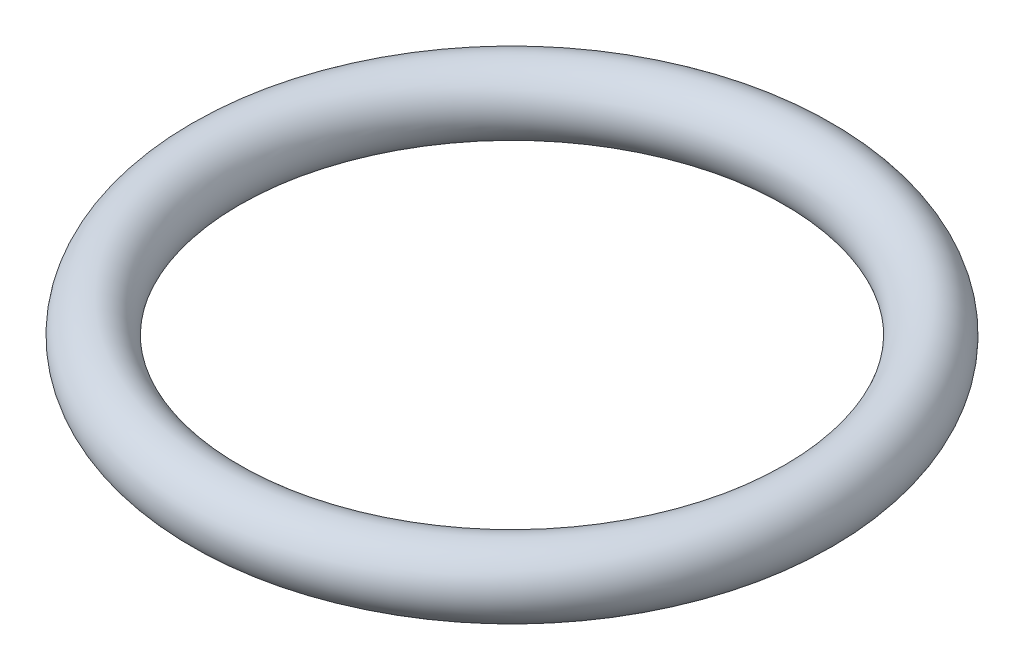
SolidWorks part; units mm, degrees
material "Rubber"
ref_plane "Front Plane" through (0, 0, 0) normal (0, 0, 1) x (1, 0, 0)
ref_plane "Top Plane" through (0, 0, 0) normal (0, 1, 0) x (1, 0, 0)
ref_plane "Right Plane" through (0, 0, 0) normal (1, 0, 0) x (0, 0, -1)
sketch "Sketch1" plane through (0, 0, 0) normal (0, 0, 1) x (1, 0, 0)
  line L0 (55, 0) -> (-55, 0) construction
  line L1 (0, 22.8759) -> (0, -24.4285) construction
  circle A0 centre (-7.8867, 0) radius 0.889
  dimension "D1" = 1.778
  dimension "D2" = 13.9954
revolve "Revolve1" add sketch "Sketch1" angle 360 about L1
ref_point "Point1"
ref_axis "Axis1" through (0, 0, 0) along (0, 1, 0)
